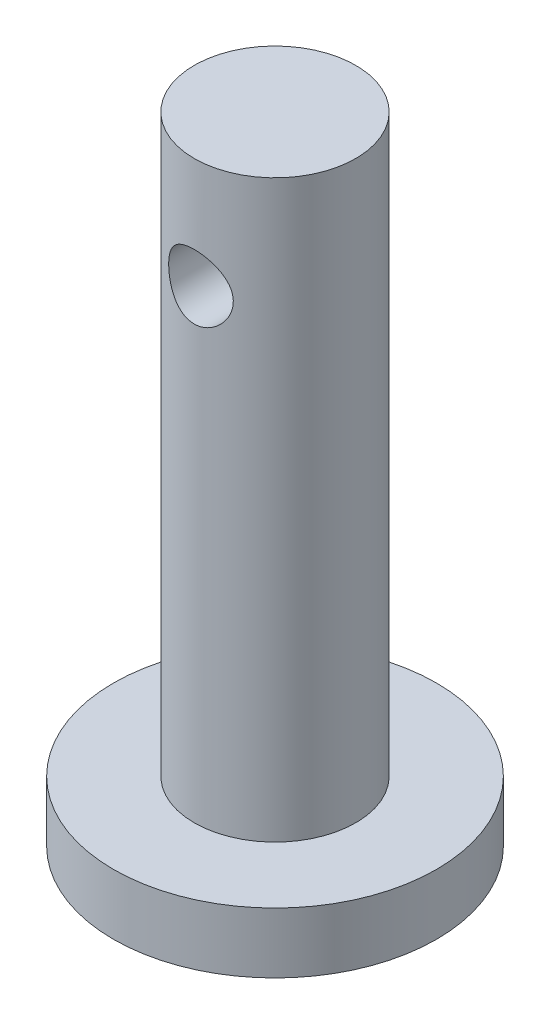
SolidWorks part; units mm, degrees
ref_plane "Plan de face" through (0, 0, 0) normal (0, 0, 1) x (1, 0, 0)
ref_plane "Plan de dessus" through (0, 0, 0) normal (0, 1, 0) x (1, 0, 0)
ref_plane "Plan de droite" through (0, 0, 0) normal (1, 0, 0) x (0, 0, -1)
sketch "Esquisse1" plane through (0, 0, 0) normal (0, 1, 0) x (1, 0, 0)
  circle A0 centre (0, 0) radius 4
  circle A1 centre (0, 0) radius 8
extrude "Boss.-Extru.1" add sketch "Esquisse1" along normal blind 3
extrude "Boss.-Extru.3" add sketch "Esquisse1<4>" along normal blind 31.5 contours A0
sketch "Esquisse1<4>" plane through (0, 0, 0) normal (0, 1, 0) x (1, 0, 0) same geometry as "Esquisse1"
sketch "Esquisse2" plane through (0, 0, 0) normal (0, 0, 1) x (1, 0, 0)
  line L0 (0, 0) -> (0, 26) construction
  circle A0 centre (0, 26) radius 1.6
extrude "Enlèv. mat.-Extru.1" cut sketch "Esquisse2" against normal blind 10 and the other way blind 10
